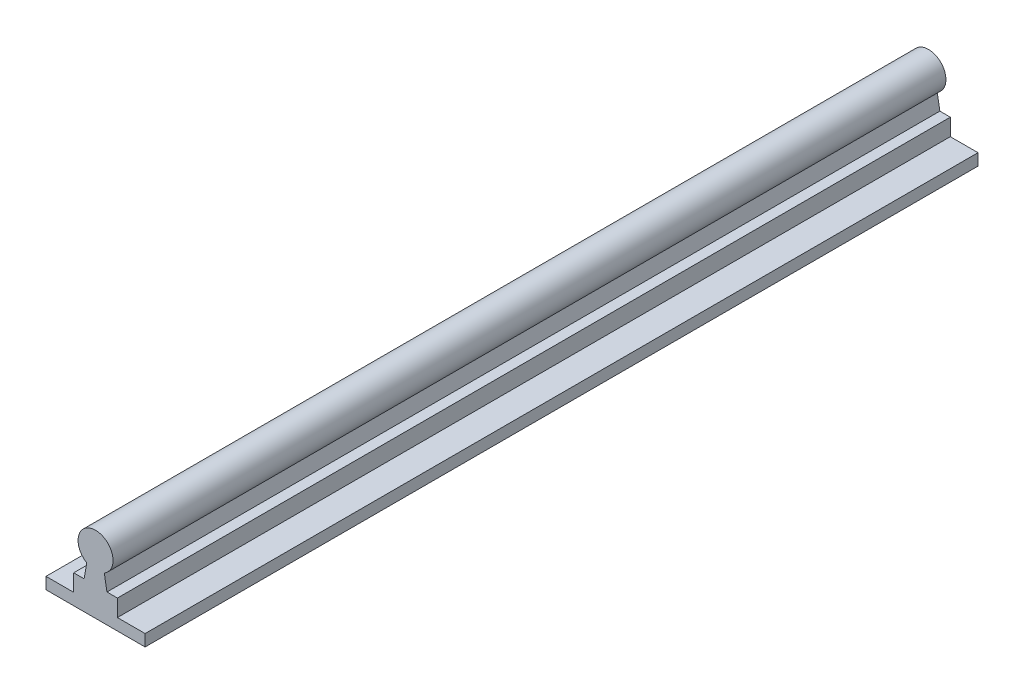
SolidWorks part; units mm, degrees
material "Chrome Stainless Steel"
ref_plane "Front Plane" through (0, 0, 0) normal (0, 0, 1) x (1, 0, 0)
ref_plane "Top Plane" through (0, 0, 0) normal (0, 1, 0) x (1, 0, 0)
ref_plane "Right Plane" through (0, 0, 0) normal (1, 0, 0) x (0, 0, -1)
sketch "Sketch1" plane through (0, 0, 0) normal (0, 0, 1) x (1, 0, 0)
  line L0 (21.3075, 0) -> (-12.6925, 0)
  line L1 (21.3075, 0) -> (21.3075, 4)
  line L2 (21.3075, 4) -> (11.8075, 4)
  line L3 (11.8075, 4) -> (11.8075, 9.8)
  line L4 (11.8075, 9.8) -> (8.2244, 9.8)
  line L5 (8.2244, 9.8) -> (7.3075, 15)
  line L6 (4.3075, 0) -> (4.3075, 36.0795) construction
  line L7 (0.3906, 9.8) -> (1.3075, 15)
  line L8 (-3.1925, 9.8) -> (0.3906, 9.8)
  line L9 (-3.1925, 4) -> (-3.1925, 9.8)
  line L10 (-12.6925, 0) -> (-12.6925, 4)
  line L11 (-12.6925, 4) -> (-3.1925, 4)
  arc A0 (7.3075, 15) -> (1.3075, 15) centre (4.3075, 20.1962) ccw
  point P17 (4.3075, 0)
  dimension "D5" = 6
  dimension "D1" = 17
  dimension "D2" = 4
  dimension "D3" = 9.8
  dimension "D4" = 15
  dimension "D6" = 3
  dimension "D8" = 20.1962
  dimension "D9" = 7.5
extrude "Boss-Extrude1" add sketch "Sketch1" along normal blind 285.75
